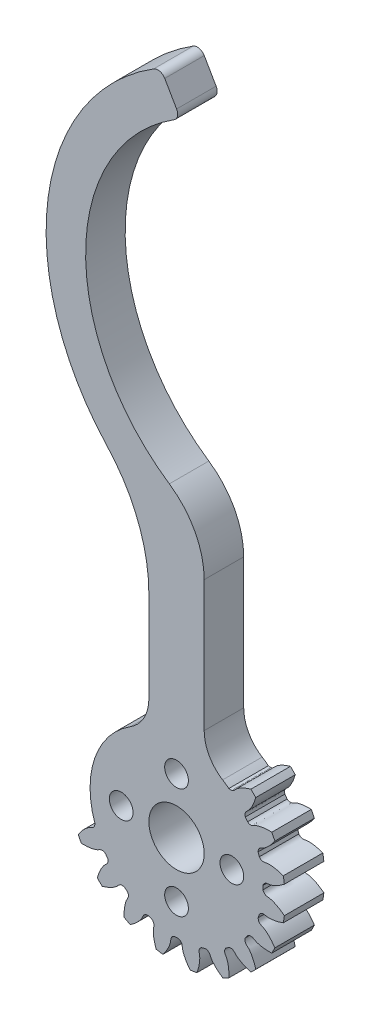
SolidWorks part; units mm, degrees
material "聚脂树脂"
ref_plane "前视基准面" through (0, 0, 0) normal (0, 0, 1) x (1, 0, 0)
ref_plane "上视基准面" through (0, 0, 0) normal (0, 1, 0) x (1, 0, 0)
ref_plane "右视基准面" through (0, 0, 0) normal (1, 0, 0) x (0, 0, -1)
other "Configuration Table"
sketch "草图1" plane through (0, 0, 0) normal (0, 0, 1) x (1, 0, 0)
  circle A0 centre (0, 0) radius 13.75
extrude "凸台-拉伸1" add sketch "草图1" along normal blind 5
ref_axis "基准轴1" through (0, 0, -1.5) along (0, 0, 1)
sketch "草图2" plane through (0, 0, 0) normal (0, 0, 1) x (1, 0, 0)
  line L0 (0, 0) -> (0, 13.75) construction
  circle A0 centre (0, 0) radius 13.75 construction
  arc A1 (0.2416, 10.9348) -> (-0.2416, 10.9348) centre (0, 0) ccw
  arc A2 (3.9764, 15.6228) -> (-3.9764, 15.6228) centre (0, 0) ccw
  spline S0 degree 3 poles (0.2416, 10.9348) (0.764, 11.1168) (0.6964, 11.4839) (0.7661, 11.8375) (0.7736, 11.8719) (0.7829, 11.9108) (0.7941, 11.954) (0.8075, 12.0015) (0.8231, 12.0532) (0.8413, 12.1091) (0.8621, 12.169) (0.8857, 12.2329) (0.9123, 12.3007) (0.9421, 12.3723) (0.9752, 12.4476) (1.0117, 12.5264) (1.0519, 12.6088) (1.0959, 12.6945) (1.1438, 12.7834) (1.1957, 12.8755) (1.2519, 12.9705) (1.3125, 13.0684) (1.3775, 13.1691) (1.4472, 13.2723) (1.5216, 13.3779) (1.601, 13.4858) (1.6853, 13.5958) (1.7747, 13.7078) (1.8694, 13.8216) (1.9693, 13.937) (2.0748, 14.0539) (2.1857, 14.1721) (2.3023, 14.2914) (2.4246, 14.4116) (2.5527, 14.5326) (2.6866, 14.6542) (2.8265, 14.7761) (2.9725, 14.8983) (3.1245, 15.0204) (3.2826, 15.1424) (3.4469, 15.2639) (3.6768, 15.427) (3.8549, 15.5454) (3.9764, 15.6228) knots 0 0 0 0 0.165916 0.170906 0.176664 0.183189 0.190482 0.198542 0.207371 0.216967 0.22733 0.238462 0.250361 0.263027 0.276462 0.290664 0.305634 0.321371 0.337876 0.355149 0.37319 0.391998 0.411574 0.431917 0.453028 0.474907 0.497554 0.520968 0.54515 0.570099 0.595817 0.622302 0.649554 0.677575 0.706363 0.735918 0.766242 0.797333 0.829191 0.861818 0.895212 0.929373 1 1 1 1
  spline S1 degree 3 poles (-0.2416, 10.9348) (-0.764, 11.1168) (-0.6964, 11.4839) (-0.7661, 11.8375) (-0.7736, 11.8719) (-0.7829, 11.9108) (-0.7941, 11.954) (-0.8075, 12.0015) (-0.8231, 12.0532) (-0.8413, 12.1091) (-0.8621, 12.169) (-0.8857, 12.2329) (-0.9123, 12.3007) (-0.9421, 12.3723) (-0.9752, 12.4476) (-1.0117, 12.5264) (-1.0519, 12.6088) (-1.0959, 12.6945) (-1.1438, 12.7834) (-1.1957, 12.8755) (-1.2519, 12.9705) (-1.3125, 13.0684) (-1.3775, 13.1691) (-1.4472, 13.2723) (-1.5216, 13.3779) (-1.601, 13.4858) (-1.6853, 13.5958) (-1.7747, 13.7078) (-1.8694, 13.8216) (-1.9693, 13.937) (-2.0748, 14.0539) (-2.1857, 14.1721) (-2.3023, 14.2914) (-2.4246, 14.4116) (-2.5527, 14.5326) (-2.6866, 14.6542) (-2.8265, 14.7761) (-2.9725, 14.8983) (-3.1245, 15.0204) (-3.2826, 15.1424) (-3.4469, 15.2639) (-3.6768, 15.427) (-3.8549, 15.5454) (-3.9764, 15.6228) knots 0 0 0 0 0.165916 0.170906 0.176664 0.183189 0.190482 0.198542 0.207371 0.216967 0.22733 0.238462 0.250361 0.263027 0.276462 0.290664 0.305634 0.321371 0.337876 0.355149 0.37319 0.391998 0.411574 0.431917 0.453028 0.474907 0.497554 0.520968 0.54515 0.570099 0.595817 0.622302 0.649554 0.677575 0.706363 0.735918 0.766242 0.797333 0.829191 0.861818 0.895212 0.929373 1 1 1 1
extrude "切除-拉伸1" cut sketch "草图2" along normal through all
pattern_circular "阵列(圆周)1" count 20 every 18 about axis through (0, 0, -1.5) along (0, 0, 1) of "切除-拉伸1"
sketch "草图6" plane through (0, 0, 0) normal (0, 0, -1) x (-1, 0, 0)
  line L0 (0, 0) -> (0, 65.9124) construction
  line L1 (0, 0) -> (39.45, 0) construction
  line L2 (0, 0) -> (-30.8379, 0) construction
  line L3 (-12.5, 0) -> (-12.5, 58.22) construction
  line L4 (3.5, 0) -> (3.5, 35.9714)
  line L5 (-3.5, 0) -> (-3.5, 35.9714)
  line L6 (-3.5, 35.9714) -> (-3.5, 73.8085)
  line L7 (-3.5, 73.8085) -> (-12.5, 58.22) construction
  line L8 (-3.5, 73.8085) -> (6.3052, 90.7916) construction
  line L9 (-3.5, 73.8085) -> (1.2022, 81.9529)
  line L10 (-3.5, 0) -> (3.5, 0)
  line L11 (-5.8534, 12.4419) -> (-3.5, 13.8006)
  line L12 (5.8534, 12.4419) -> (3.5, 13.8006)
  line L13 (1.2022, 81.9529) -> (2, 83.3347)
  line L14 (-12.5, 58.22) -> (11.7991, 33.9209) construction
  circle A0 centre (0, 0) radius 12.5 construction
  circle A1 centre (-12.5, 58.22) radius 24 construction
  circle A2 centre (-12.5, 58.22) radius 27.4044 construction
  arc A3 (1.2022, 81.9529) -> (3.5, 35.9714) centre (-12.5, 58.22) cw
  arc A4 (-0.5, 79.0046) -> (-3.5, 35.9714) centre (-12.5, 58.22) cw
  circle A5 centre (-12.5, 58.22) radius 29
  spline S0 degree 3 poles (1668.4324, 1107.449) (-22.4355, -9.6532) (-2.0511, 6.8358) (-4.3931, 11.033) (-4.4189, 11.076) (-4.4589, 11.1387) (-4.5098, 11.2131) (-4.5827, 11.3111) (-4.6712, 11.4208) (-4.7765, 11.541) (-4.8994, 11.6706) (-5.0408, 11.8083) (-5.2016, 11.9528) (-5.3825, 12.1027) (-5.5474, 12.2287) (-5.6899, 12.331) (-25.6073, 26.0378) (-114.7142, -63.0586) (1854.1098, 747.2788) knots -2.172632 -2.172632 -2.172632 -2.172632 0.165916 0.170906 0.183189 0.190482 0.207371 0.22733 0.250361 0.276462 0.305634 0.337876 0.37319 0.411574 0.453028 0.474907 0.497554 12.30377 12.30377 12.30377 12.30377 only from (-3.6089, 10.325) to (-5.8534, 12.4419) construction
  spline S1 degree 3 poles (-3.5, 10.3269) (-4.1564, 10.2919) (-4.2008, 10.6883) (-4.3931, 11.033) (-4.4189, 11.076) (-4.4589, 11.1387) (-4.5098, 11.2131) (-4.5827, 11.3111) (-4.6712, 11.4208) (-4.7765, 11.541) (-4.8994, 11.6706) (-5.0408, 11.8083) (-5.2016, 11.9528) (-5.3825, 12.1027) (-5.5842, 12.2567) (-5.7442, 12.3691) (-5.8366, 12.4308) (-5.8534, 12.4419) knots -0.010289 -0.010289 -0.010289 -0.010289 0.165916 0.170906 0.183189 0.190482 0.207371 0.22733 0.250361 0.276462 0.305634 0.337876 0.37319 0.411574 0.453028 0.497554 0.507432 0.507432 0.507432 0.507432
  spline S2 degree 3 poles (-1668.4324, 1107.449) (22.4355, -9.6532) (2.0511, 6.8358) (4.3931, 11.033) (4.4189, 11.076) (4.4589, 11.1387) (4.5098, 11.2131) (4.5827, 11.3111) (4.6712, 11.4208) (4.7765, 11.541) (4.8994, 11.6706) (5.0408, 11.8083) (5.2016, 11.9528) (5.3825, 12.1027) (5.5474, 12.2287) (5.6899, 12.331) (25.6073, 26.0378) (114.7142, -63.0586) (-1854.1098, 747.2788) knots -1.680063 -1.680063 -1.680063 -1.680063 0.658484 0.663474 0.675757 0.68305 0.699939 0.719899 0.742929 0.76903 0.798202 0.830445 0.865758 0.904142 0.945597 0.967475 0.990122 12.796339 12.796339 12.796339 12.796339 only from (3.6089, 10.325) to (5.8534, 12.4419) construction
  spline S3 degree 3 poles (3.5, 10.3269) (4.1564, 10.2919) (4.2008, 10.6883) (4.3931, 11.033) (4.4189, 11.076) (4.4589, 11.1387) (4.5098, 11.2131) (4.5827, 11.3111) (4.6712, 11.4208) (4.7765, 11.541) (4.8994, 11.6706) (5.0408, 11.8083) (5.2016, 11.9528) (5.3825, 12.1027) (5.5842, 12.2567) (5.7442, 12.3691) (5.8366, 12.4308) (5.8534, 12.4419) knots 0.482279 0.482279 0.482279 0.482279 0.658484 0.663474 0.675757 0.68305 0.699939 0.719899 0.742929 0.76903 0.798202 0.830445 0.865758 0.904142 0.945597 0.990122 1 1 1 1
  dimension "D1" = 25
  dimension "D4" = 48
  dimension "D5" = 30
  dimension "D8" = 58
  dimension "D2" = 7
  dimension "D3" = 58.22
  dimension "D6" = 60
  dimension "D7" = 60
  dimension "D9" = 45
extrude "凸台-拉伸2" add sketch "草图6" against normal blind 5 contours A3 L9 L6 L5 L10 L4 | S1 L5 L11 | L4 S3 L12 | L5 A5 L4 A3 L9 A4 | L4 A5 L13 A3 region at (-0.0611, 16.0891, 0) region at (-4.2531, 12.1172, 0) region at (4.2531, 12.1172, 0) region at (0.1232, 32.5977, 0) region at (-4.0162, 35.0023, 0)
ref_plane "基准面1" through (12.5, 0, 0) normal (1, 0, 0) x (0, 0, -1)
sketch "草图4" plane through (0, 0, 5) normal (0, 0, 1) x (1, 0, 0)
  line L0 (0, 0) -> (0, 14.4175) construction
  line L1 (0, 0) -> (19.7904, 0) construction
  circle A0 centre (0, 0) radius 9
  circle A1 centre (0, 0) radius 3.5
  circle A2 centre (0, 7) radius 1.5
  circle A3 centre (7, 0) radius 1.5
  circle A4 centre (0, -7) radius 1.5
  circle A5 centre (-7, 0) radius 1.5
  dimension "D1" = 18
  dimension "D2" = 7
  dimension "D3" = 3
  dimension "D4" = 3
  dimension "D5" = 7
  dimension "D6" = 7
extrude "切除-拉伸2" cut sketch "草图4" against normal blind 20 contours A1 | A5 | A2 | A3 | A4
ref_plane "基准面2" through (0, 0, 9) normal (0, 0, 1) x (1, 0, 0)
sketch "草图17" plane through (0, 0, 5) normal (0, 0, 1) x (1, 0, 0)
  line L0 (0, 0) -> (-6.6228, 8.7044)
  line L1 (-6.6228, 8.7044) -> (-11.857, 15.5837)
  line L2 (0, 0) -> (-10.325, -3.6089)
  line L3 (-10.325, -3.6089) -> (-17.9409, -6.2709)
  circle A0 centre (0, 0) radius 10.9375
  arc A1 (-6.2318, 8.9885) -> (-6.6228, 8.7044) centre (0, 0) ccw construction
  circle A2 centre (0, 0) radius 17.5
  dimension "D1" = 35
extrude "切除-拉伸5" cut sketch "草图17" against normal blind 10 contours L1 A2 L3 A0 region at (-12.9643, 3.8979, 5)
fillet "圆角3" radius 10 1 edges at (3.5, 35.9714, 2.5)
fillet "圆角4" radius 1 2 edges at (-2, 83.3347, 2.5) (0.5, 79.0046, 2.5)
sketch "草图20" plane through (0, 0, 0) normal (0, 0, -1) x (-1, 0, 0)
  line L0 (-3.5, 13.8006) -> (-3.5, 10.3624)
  line L1 (3.5, 13.8006) -> (3.5, 10.3624)
  line L2 (5.8534, 12.4419) -> (3.5, 13.8006) construction
  line L3 (-5.8534, 12.4419) -> (-3.5, 13.8006) construction
  line L4 (5.8534, 12.4419) -> (3.5, 13.8006)
  line L5 (-5.8534, 12.4419) -> (-3.5, 13.8006)
  circle A0 centre (0, 0) radius 10.9375
  arc A1 (10.325, -3.6089) -> (6.2318, 8.9885) centre (0, 0) ccw construction
  arc A2 (6.6252, 12.0486) -> (5.8534, 12.4419) centre (0, 0) ccw construction
  arc A3 (-5.8534, 12.4419) -> (-6.6252, 12.0486) centre (0, 0) ccw construction
  arc A4 (6.6252, 12.0486) -> (5.8534, 12.4419) centre (0, 0) ccw
  arc A5 (-5.8534, 12.4419) -> (-6.6252, 12.0486) centre (0, 0) ccw
  spline S0 degree 3 poles (1876.625, -698.848) (-20.9969, 12.4766) (4.3246, 5.6774) (6.3437, 10.0391) (6.3633, 10.0853) (6.3905, 10.1545) (6.4208, 10.2394) (6.4573, 10.356) (6.4939, 10.4921) (6.5293, 10.6479) (6.5619, 10.8235) (6.5902, 11.0188) (6.6126, 11.2338) (6.6276, 11.4683) (6.6325, 11.6758) (6.6315, 11.8512) (6.0134, 36.0214) (-118.4428, 55.7409) (1694.3797, -1060.7669) knots -2.172632 -2.172632 -2.172632 -2.172632 0.165916 0.170906 0.183189 0.190482 0.207371 0.22733 0.250361 0.276462 0.305634 0.337876 0.37319 0.411574 0.453028 0.474907 0.497554 12.30377 12.30377 12.30377 12.30377 only from (6.2318, 8.9885) to (6.6252, 12.0486) construction
  spline S1 degree 3 poles (-1876.625, -698.848) (20.9969, 12.4766) (-4.3246, 5.6774) (-6.3437, 10.0391) (-6.3633, 10.0853) (-6.3905, 10.1545) (-6.4208, 10.2394) (-6.4573, 10.356) (-6.4939, 10.4921) (-6.5293, 10.6479) (-6.5619, 10.8235) (-6.5902, 11.0188) (-6.6126, 11.2338) (-6.6276, 11.4683) (-6.6325, 11.6758) (-6.6315, 11.8512) (-6.0134, 36.0214) (118.4428, 55.7409) (-1694.3797, -1060.7669) knots -1.680063 -1.680063 -1.680063 -1.680063 0.658484 0.663474 0.675757 0.68305 0.699939 0.719899 0.742929 0.76903 0.798202 0.830445 0.865758 0.904142 0.945597 0.967475 0.990122 12.796339 12.796339 12.796339 12.796339 only from (-6.2318, 8.9885) to (-6.6252, 12.0486) construction
  spline S2 degree 3 poles (6.2318, 8.9885) (5.9162, 9.4428) (6.1867, 9.7) (6.3437, 10.0391) (6.3633, 10.0853) (6.3905, 10.1545) (6.4208, 10.2394) (6.4573, 10.356) (6.4939, 10.4921) (6.5293, 10.6479) (6.5619, 10.8235) (6.5902, 11.0188) (6.6126, 11.2338) (6.6276, 11.4683) (6.6336, 11.722) (6.6305, 11.9176) (6.6261, 12.0285) (6.6252, 12.0486) knots 0 0 0 0 0.165916 0.170906 0.183189 0.190482 0.207371 0.22733 0.250361 0.276462 0.305634 0.337876 0.37319 0.411574 0.453028 0.497554 0.507432 0.507432 0.507432 0.507432
  spline S3 degree 3 poles (-6.2318, 8.9885) (-5.9162, 9.4428) (-6.1867, 9.7) (-6.3437, 10.0391) (-6.3633, 10.0853) (-6.3905, 10.1545) (-6.4208, 10.2394) (-6.4573, 10.356) (-6.4939, 10.4921) (-6.5293, 10.6479) (-6.5619, 10.8235) (-6.5902, 11.0188) (-6.6126, 11.2338) (-6.6276, 11.4683) (-6.6336, 11.722) (-6.6305, 11.9176) (-6.6261, 12.0285) (-6.6252, 12.0486) knots 0.492568 0.492568 0.492568 0.492568 0.658484 0.663474 0.675757 0.68305 0.699939 0.719899 0.742929 0.76903 0.798202 0.830445 0.865758 0.904142 0.945597 0.990122 1 1 1 1
extrude "切除-拉伸7" cut sketch "草图20" against normal blind 10 contours S3 A0 L0 L5 A5 | A0 S2 A4 L4 L1 region at (4.956, 11.3958, 0) region at (-4.956, 11.3958, 0)
fillet "圆角7" radius 5 2 edges at (-3.5, 10.3624, 2.5) (3.5, 10.3624, 2.5)
fillet "圆角8" radius 20 1 edges at (-3.5, 34.0332, 2.5)
